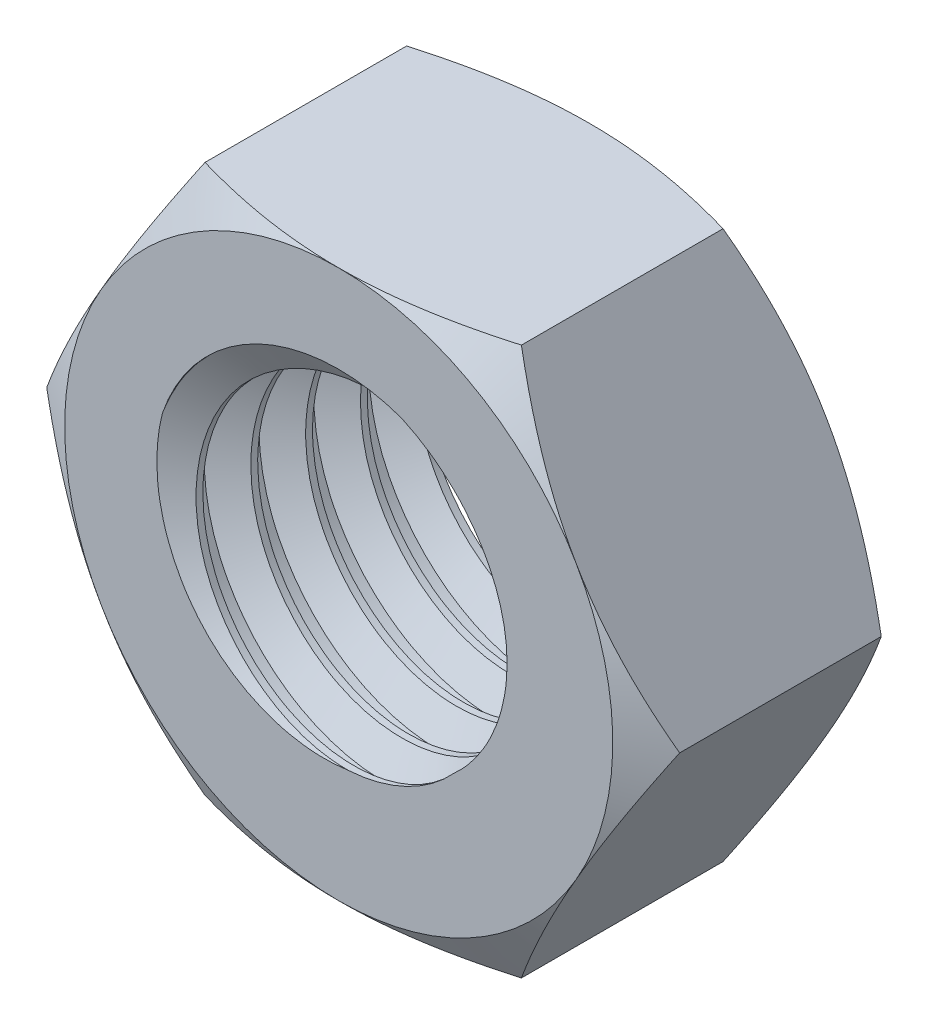
SolidWorks part; units mm, degrees
ref_plane "前视基准面" through (0, 0, 0) normal (0, 0, 1) x (1, 0, 0)
ref_plane "上视基准面" through (0, 0, 0) normal (0, 1, 0) x (1, 0, 0)
ref_plane "右视基准面" through (0, 0, 0) normal (1, 0, 0) x (0, 0, -1)
sketch "草图1" plane through (0, 0, 0) normal (0, 0, 1) x (1, 0, 0)
  line L1 (4.0415, 0) -> (2.0207, 3.5)
  line L2 (2.0207, 3.5) -> (-2.0207, 3.5)
  line L3 (-2.0207, 3.5) -> (-4.0415, 0)
  line L4 (-4.0415, 0) -> (-2.0207, -3.5)
  line L5 (-2.0207, -3.5) -> (2.0207, -3.5)
  line L6 (2.0207, -3.5) -> (4.0415, 0)
  circle A0 centre (0, 0) radius 3.5 construction
  dimension "D1" = 7
extrude "拉伸1" add sketch "草图1" along normal blind 3.2
sketch "草图2" plane through (0, 0, 0) normal (0, 0, -1) x (-1, 0, 0)
  circle A0 centre (0, 0) radius 3.5
  dimension "D1" = 7
sketch "草图3" plane through (0, 0, 0) normal (0, 1, 0) x (1, 0, 0)
  line L0 (3.5, 0) -> (4.0415, -0.3126)
  line L1 (3.5, 0) -> (-3.5, 0)
  line L2 (3.5, 0) -> (-3.5, 0)
  line L3 (4.0415, -3.2) -> (4.0415, 0) construction
  line L4 (3.5, 0) -> (4.0415, 0)
  line L5 (4.0415, 0) -> (4.0415, -0.3126)
  line L6 (0, 4.959) -> (0, -21.1771) construction
  dimension "D2" = 30
  dimension "D1" = 0
revolve "切除-旋转1" cut sketch "草图3" angle 360 about L6
sketch "草图4" plane through (0, 0, 3.2) normal (0, 0, 1) x (1, 0, 0)
  circle A0 centre (0, 0) radius 3.5
  dimension "D1" = 7
sketch "草图5" plane through (0, 0, 0) normal (0, 1, 0) x (1, 0, 0)
  line L0 (3.5, -3.2) -> (4.0415, -2.8874)
  line L1 (-3.5, -3.2) -> (3.5, -3.2)
  line L2 (-3.5, -3.2) -> (3.5, -3.2)
  line L3 (4.0415, -3.2) -> (4.0415, -0.3126) construction
  line L4 (3.5, -3.2) -> (4.0415, -3.2)
  line L5 (4.0415, -2.8874) -> (4.0415, -3.2)
  line L6 (0, 5.5944) -> (0, -24.6427) construction
  dimension "D2" = 30
  dimension "D1" = 0
revolve "切除-旋转2" cut sketch "草图5" angle 360 about L6
sketch "草图6" plane through (0, 0, 3.2) normal (0, 0, 1) x (1, 0, 0)
  circle A0 centre (0, 0) radius 2
  dimension "D1" = 4
extrude "切除-拉伸1" cut sketch "草图6" against normal through all
sketch "草图7" plane through (0, 0, 0) normal (1, 0, 0) x (0, 0, -1)
  line L0 (-4.9903, -2) -> (2.3037, -2) construction
  line L1 (-3.2, -2) -> (0, -2) construction
  line L2 (0, -11.5678) -> (0, -23.4371) construction
  line L3 (0, -3.5) -> (0, -1.75) construction
  line L4 (0, -1.75) -> (0, 1.75) construction
  line L5 (-0.0875, -2.3789) -> (-0.3063, -2)
  line L6 (0.0875, -2.3789) -> (0.3063, -2)
  line L7 (-0.3063, -2) -> (0.3063, -2)
  line L8 (-0.0875, -2.3789) -> (0.0875, -2.3789)
  dimension "D1" = 30
  dimension "D2" = 30
  dimension "D3" = 0.6125
  dimension "D4" = 0.175
sketch "草图8" plane through (0, 0, 0) normal (0, 0, -1) x (-1, 0, 0)
  circle A0 centre (0, 0) radius 2
  dimension "D1" = 4
curve "螺旋线1" pitch 0.7 height 3.2 turns 4.5714
sweep "切除-扫描1" cut profiles "草图7" path "螺旋线1"
